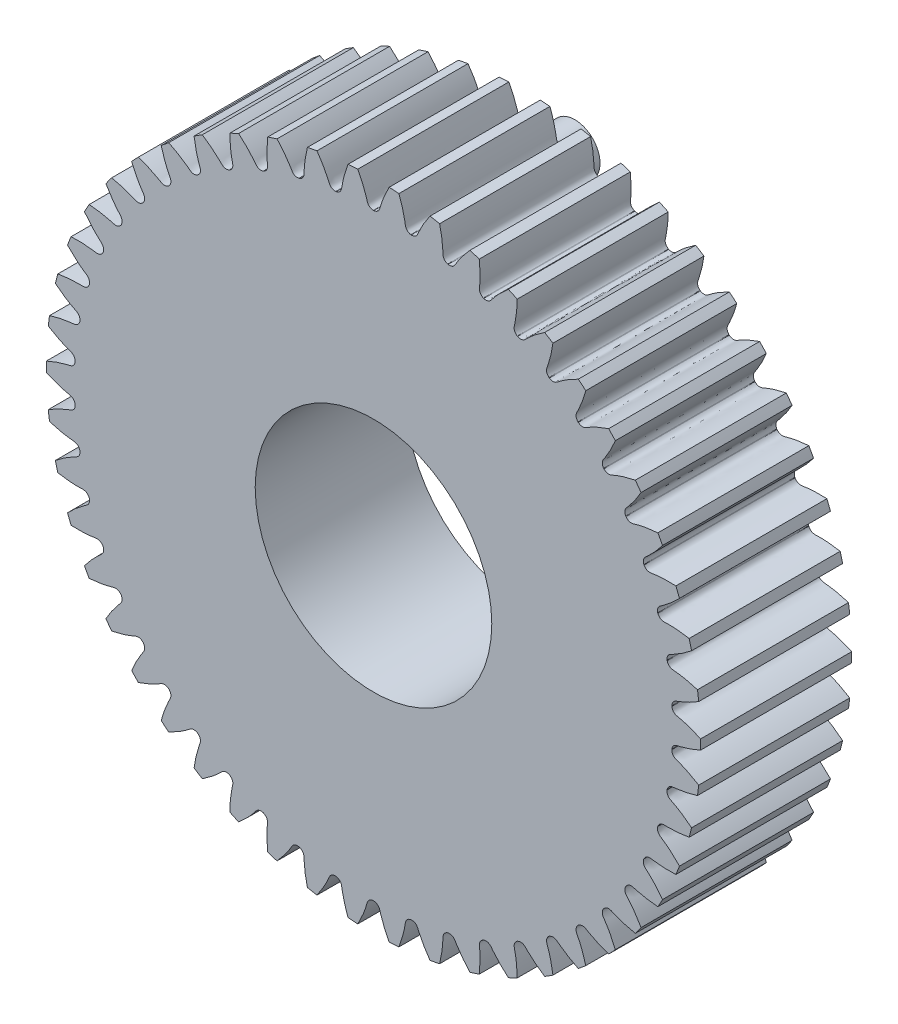
SolidWorks part; units mm, degrees
ref_plane "前视基准面" through (0, 0, 0) normal (0, 0, 1) x (1, 0, 0)
ref_plane "上视基准面" through (0, 0, 0) normal (0, 1, 0) x (1, 0, 0)
ref_plane "右视基准面" through (0, 0, 0) normal (1, 0, 0) x (0, 0, -1)
sketch "草图1" plane through (0, 0, 0) normal (0, 0, 1) x (1, 0, 0)
  circle A0 centre (0, 0) radius 65
extrude "凸台-拉伸1" add sketch "草图1" along normal blind 30
ref_axis "基准轴1" through (0, 0, 30) along (0, 0, -1)
sketch "草图2" plane through (0, 0, 0) normal (0, 0, 1) x (1, 0, 0)
  line L0 (0, 0) -> (0, 65) construction
  circle A0 centre (0, 0) radius 65 construction
  arc A1 (0.0456, 59.375) -> (-0.0456, 59.375) centre (0, 0) ccw
  arc A2 (9.647, 73.5086) -> (-9.647, 73.5086) centre (0, 0) ccw
  spline S0 degree 3 poles (0.0456, 59.375) (1.0876, 59.5023) (1.2207, 60.2889) (1.487, 61.1469) (1.5967, 61.4824) (1.7214, 61.8375) (1.8612, 62.2121) (2.0171, 62.6057) (2.19, 63.0178) (2.3805, 63.4478) (2.5896, 63.8952) (2.818, 64.3594) (3.0663, 64.8398) (3.3355, 65.3359) (3.6261, 65.8468) (3.9389, 66.372) (4.2745, 66.9109) (4.6337, 67.4625) (5.017, 68.0264) (5.4251, 68.6016) (5.8586, 69.1874) (6.3181, 69.783) (6.8042, 70.3877) (7.3173, 71.0005) (7.858, 71.6206) (8.6269, 72.4677) (9.2308, 73.0937) (9.647, 73.5086) knots 0 0 0 0 0.116496 0.135538 0.155939 0.177697 0.200814 0.225289 0.251122 0.278313 0.306862 0.33677 0.368035 0.400659 0.434641 0.469981 0.506679 0.544736 0.584151 0.624923 0.667054 0.710544 0.755391 0.801596 0.84916 0.898082 1 1 1 1
  spline S1 degree 3 poles (-0.0456, 59.375) (-1.0876, 59.5023) (-1.2207, 60.2889) (-1.487, 61.1469) (-1.5967, 61.4824) (-1.7214, 61.8375) (-1.8612, 62.2121) (-2.0171, 62.6057) (-2.19, 63.0178) (-2.3805, 63.4478) (-2.5896, 63.8952) (-2.818, 64.3594) (-3.0663, 64.8398) (-3.3355, 65.3359) (-3.6261, 65.8468) (-3.9389, 66.372) (-4.2745, 66.9109) (-4.6337, 67.4625) (-5.017, 68.0264) (-5.4251, 68.6016) (-5.8586, 69.1874) (-6.3181, 69.783) (-6.8042, 70.3877) (-7.3173, 71.0005) (-7.858, 71.6206) (-8.6269, 72.4677) (-9.2308, 73.0937) (-9.647, 73.5086) knots 0 0 0 0 0.116496 0.135538 0.155939 0.177697 0.200814 0.225289 0.251122 0.278313 0.306862 0.33677 0.368035 0.400659 0.434641 0.469981 0.506679 0.544736 0.584151 0.624923 0.667054 0.710544 0.755391 0.801596 0.84916 0.898082 1 1 1 1
extrude "切除-拉伸1" cut sketch "草图2" along normal through all
pattern_circular "阵列(圆周)1" count 50 every 7.2 about axis through (0, 0, 30) along (0, 0, -1) of "切除-拉伸1"
sketch "草图3" plane through (0, 0, 0) normal (0, 0, 1) x (1, 0, 0)
  circle A0 centre (0, 0) radius 62.5 construction
  dimension "Dn" = 125
sketch "草图4" plane through (0, 0, 30) normal (0, 0, 1) x (1, 0, 0)
  circle A0 centre (0, 0) radius 50 construction
  circle A1 centre (-50, 0) radius 5
  dimension "D1" = 100
  dimension "D2" = 10
sketch "草图6" plane through (0, 0, 0) normal (0, 0, -1) x (-1, 0, 0)
  point P0 (0, 0)
sketch "草图7" plane through (0, 0, 0) normal (0, 0, -1) x (-1, 0, 0)
  circle A0 centre (0, 0) radius 50 construction
  circle A1 centre (50, 0) radius 5
  dimension "D1" = 100
  dimension "D2" = 10
extrude "凸台-拉伸3" add sketch "草图7" along normal blind 60
sketch "草图8" plane through (0, 0, 0) normal (0, 0, -1) x (-1, 0, 0)
  circle A0 centre (0, 0) radius 23.5
  dimension "D1" = 47
extrude "切除-拉伸2" cut sketch "草图8" against normal through all
